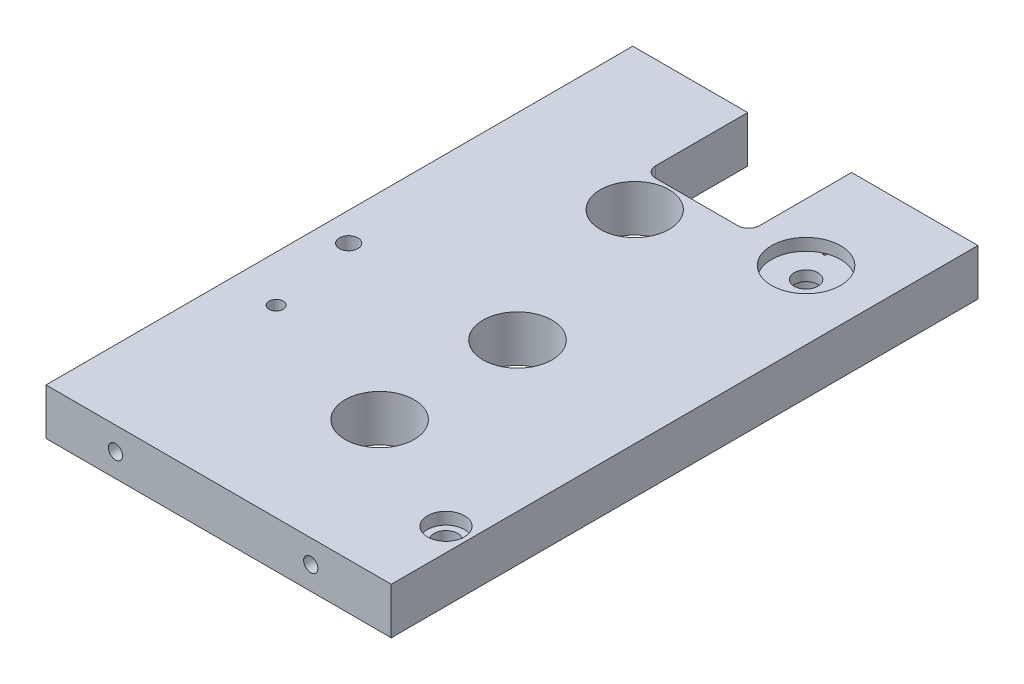
SolidWorks part; units mm, degrees
material "1060 Alloy"
ref_plane "Front Plane" through (0, 0, 0) normal (0, 0, 1) x (1, 0, 0)
ref_plane "Top Plane" through (0, 0, 0) normal (0, 1, 0) x (1, 0, 0)
ref_plane "Right Plane" through (0, 0, 0) normal (1, 0, 0) x (0, 0, -1)
sketch "Sketch1" plane through (0, 0, 0) normal (0, 0, 1) x (1, 0, 0)
  line L0 (-233.4699, -616.5) -> (-342.6239, -616.5) construction
  line L1 (-234.625, -610.1) -> (-329.875, -610.1)
  line L2 (-234.625, -610.1) -> (-234.625, -622.9)
  line L3 (-234.625, -622.9) -> (-329.875, -622.9)
  line L4 (-329.875, -610.1) -> (-329.875, -622.9)
  line L5 (-282.25, -610.1) -> (-282.25, -622.9) construction
  circle A0 centre (-307.5, -616.5) radius 3.1 construction
  circle A3 centre (-257, -616.5) radius 3.1 construction
  circle A4 centre (-244.2, -616.5) radius 2.395
  circle A5 centre (-257, -616.5) radius 3.1
  circle A6 centre (-307.5, -616.5) radius 3.1
  circle A7 centre (-320.5, -616.5) radius 2.395
  circle A10 centre (-320.5, -616.5) radius 3.425 construction
  circle A11 centre (-244.2, -616.5) radius 3.425 construction
  dimension "D3" = 4.79
  dimension "D1" = 12.8
  dimension "D2" = 95.25
extrude "Boss-Extrude1" add sketch "Sketch1" along normal blind 161.88 contours L2 L3 L4 L1
extrude "Cut-Extrude1" cut sketch "Sketch1<3>" along normal blind 20.2 contours A6 | A5 region at (-257, -616.5, 0) region at (-307.5, -616.5, 0)
sketch "Sketch1<3>" plane through (0, 0, 0) normal (0, 0, 1) x (1, 0, 0) same geometry as "Sketch1"
extrude "Cut-Extrude2" cut sketch "Sketch1<4>" along normal blind 21.5 contours A4 | A7 region at (-244.2, -616.5, 0) region at (-320.5, -616.5, 0)
sketch "Sketch1<4>" plane through (0, 0, 0) normal (0, 0, 1) x (1, 0, 0) same geometry as "Sketch1"
sketch "Sketch2" plane through (0, -610.1, 0) normal (0, 1, 0) x (1, 0, 0)
  line L0 (-234.625, 0) -> (-329.875, 0) construction
  line L1 (-269.505, 0) -> (-298.155, 0)
  line L2 (-269.505, 0) -> (-269.505, -25.4)
  line L3 (-272.505, -28.4) -> (-295.155, -28.4)
  line L4 (-298.155, 0) -> (-298.155, -25.4)
  line L5 (-272.505, -28.4) -> (-269.505, -28.4) construction
  line L6 (-269.505, -28.4) -> (-269.505, -25.4) construction
  line L7 (-295.155, -28.4) -> (-298.155, -28.4) construction
  line L8 (-298.155, -28.4) -> (-298.155, -25.4) construction
  line L9 (-275.57, -133.66) -> (-275.57, -161.88) construction
  line L10 (-234.625, -161.88) -> (-234.625, 0) construction
  line L11 (-329.875, -161.88) -> (-329.875, 0) construction
  line L12 (-234.625, -161.88) -> (-329.875, -161.88) construction
  line L13 (-266.045, -124.135) -> (-234.625, -124.135) construction
  line L14 (-266.045, -86.105) -> (-234.625, -86.105) construction
  line L15 (-275.57, -95.63) -> (-275.57, -161.88) construction
  circle A0 centre (-275.57, -124.135) radius 9.525
  circle A1 centre (-275.57, -86.105) radius 9.525
  arc A2 (-298.155, -25.4) -> (-295.155, -28.4) centre (-295.155, -25.4) ccw
  arc A3 (-272.505, -28.4) -> (-269.505, -25.4) centre (-272.505, -25.4) ccw
  dimension "D1" = 3
  dimension "D5" = 19.05
  dimension "D2" = 34.88
  dimension "D3" = 31.72
  dimension "D4" = 28.4
  dimension "D6" = 28.22
  dimension "D7" = 31.42
  dimension "D8" = 66.25
  dimension "D9" = 31.42
extrude "Cut-Extrude3" cut sketch "Sketch2" against normal up to next
sketch "Sketch3" plane through (0, -610.1, 0) normal (0, 1, 0) x (-1, 0, 0)
  line L0 (244.025, 28.505) -> (234.625, 28.505) construction
  line L1 (234.625, 161.88) -> (234.625, 0) construction
  line L2 (235.835, 140.49) -> (234.625, 140.49) construction
  line L3 (240.925, 145.58) -> (240.925, 161.88) construction
  line L4 (234.625, 161.88) -> (329.875, 161.88) construction
  line L5 (253.55, 38.03) -> (253.55, 161.88) construction
  line L6 (317.175, 111.08) -> (329.875, 111.08) construction
  line L7 (329.875, 161.88) -> (329.875, 0) construction
  line L8 (321.975, 86.28) -> (329.875, 86.28) construction
  line L9 (317.175, 111.08) -> (317.175, 161.88) construction
  line L10 (321.975, 86.28) -> (321.975, 161.88) construction
  circle A0 centre (240.925, 140.49) radius 3.265
  circle A1 centre (253.55, 28.505) radius 3.265
  circle A2 centre (240.925, 140.49) radius 5.09 construction
  circle A3 centre (253.55, 28.505) radius 9.525 construction
  circle A4 centre (317.175, 111.08) radius 1.96
  circle A5 centre (321.975, 86.28) radius 2.56
  dimension "D1" = 3.92
  dimension "D2" = 6.53
  dimension "D3" = 10.18
  dimension "D4" = 19.05
  dimension "D9" = 5.12
  dimension "D5" = 1.21
  dimension "D6" = 9.4
  dimension "D7" = 123.85
  dimension "D8" = 16.3
  dimension "D10" = 75.6
  dimension "D11" = 7.9
  dimension "D12" = 50.8
  dimension "D13" = 12.7
extrude "Cut-Extrude4" cut sketch "Sketch3" against normal up to next
sketch "Sketch4" plane through (0, -610.1, 0) normal (0, 1, 0) x (-1, 0, 0)
  circle A0 centre (253.55, 28.505) radius 9.525
  circle A1 centre (240.925, 140.49) radius 5.09
  circle A2 centre (253.55, 28.505) radius 9.525 construction
  circle A4 centre (240.925, 140.49) radius 5.09 construction
extrude "Cut-Extrude5" cut sketch "Sketch4" against normal blind 3.32
sketch "Sketch5" plane through (0, -622.9, 0) normal (0, -1, 0) x (1, 0, 0)
  circle A0 centre (-240.925, 140.49) radius 5.31
  circle A1 centre (-253.55, 28.505) radius 5.31
  circle A2 centre (-240.925, 140.49) radius 3.265 construction
  circle A3 centre (-253.55, 28.505) radius 3.265 construction
  dimension "D1" = 10.62
extrude "Cut-Extrude6" cut sketch "Sketch5" against normal blind 6.65
sketch "Sketch6" plane through (0, 0, 161.88) normal (0, 0, 1) x (1, 0, 0)
  circle A0 centre (-310.715, -616.48) radius 1.965
  circle A1 centre (-256.825, -616.48) radius 1.965
  circle A3 centre (-256.825, -616.48) radius 2.795 construction
  circle A4 centre (-310.715, -616.48) radius 2.795 construction
  dimension "D3" = 3.93
extrude "Cut-Extrude7" cut sketch "Sketch6" against normal blind 17.25
sketch "Sketch7" plane through (-329.875, 0, 0) normal (-1, 0, 0) x (0, 0, 1)
  line L0 (161.88, -616.5) -> (142.28, -616.5) construction
  line L1 (161.88, -610.1) -> (161.88, -622.9) construction
  circle A0 centre (142.28, -616.5) radius 1.97
  dimension "D1" = 3.94
  dimension "D2" = 19.6
extrude "Cut-Extrude8" cut sketch "Sketch7" against normal blind 15.87
ref_plane "Plane1" through (0, -616.5, 0) normal (0, 1, 0) x (-1, 0, 0)
sketch "Sketch8" plane through (0, -616.5, 0) normal (0, 1, 0) x (-1, 0, 0)
  line L0 (234.625, 57.29) -> (221.025, 57.29)
  line L1 (234.625, 57.29) -> (234.625, 52.09)
  line L2 (234.625, 161.88) -> (234.625, 0) construction
  line L3 (234.625, 57.29) -> (259.3185, 57.29) construction
  line L4 (234.625, 52.09) -> (233.835, 52.09)
  line L5 (233.835, 52.09) -> (233.835, 52.925)
  line L6 (233.835, 52.925) -> (232.295, 52.925)
  line L7 (232.295, 52.925) -> (232.2758, 52.475)
  line L8 (232.2758, 52.475) -> (228.8458, 52.475)
  line L9 (221.025, 57.29) -> (221.025, 54.59)
  line L10 (228.8458, 52.475) -> (228.8458, 75.3879) construction
  line L11 (228.8458, 75.3879) -> (230.8458, 75.3879) construction
  arc A0 (221.025, 54.59) -> (228.8458, 52.475) centre (230.8458, 75.3879) ccw
  dimension "D9" = 23
  dimension "D1" = 10.4
  dimension "D2" = 8.73
  dimension "D3" = 9.63
  dimension "D4" = 5.4
  dimension "D5" = 13.6
  dimension "D6" = 0.79
  dimension "D7" = 1.54
  dimension "D8" = 3.43
  dimension "D10" = 57.29
  dimension "D11" = 2
sketch "Sketch9" plane through (0, -622.9, 0) normal (0, -1, 0) x (1, 0, 0)
  circle A0 centre (-290.57, 38.77) radius 9.5
  circle A1 centre (-290.57, 38.77) radius 9.5 construction
extrude "Cut-Extrude9" cut sketch "Sketch9" against normal through all
